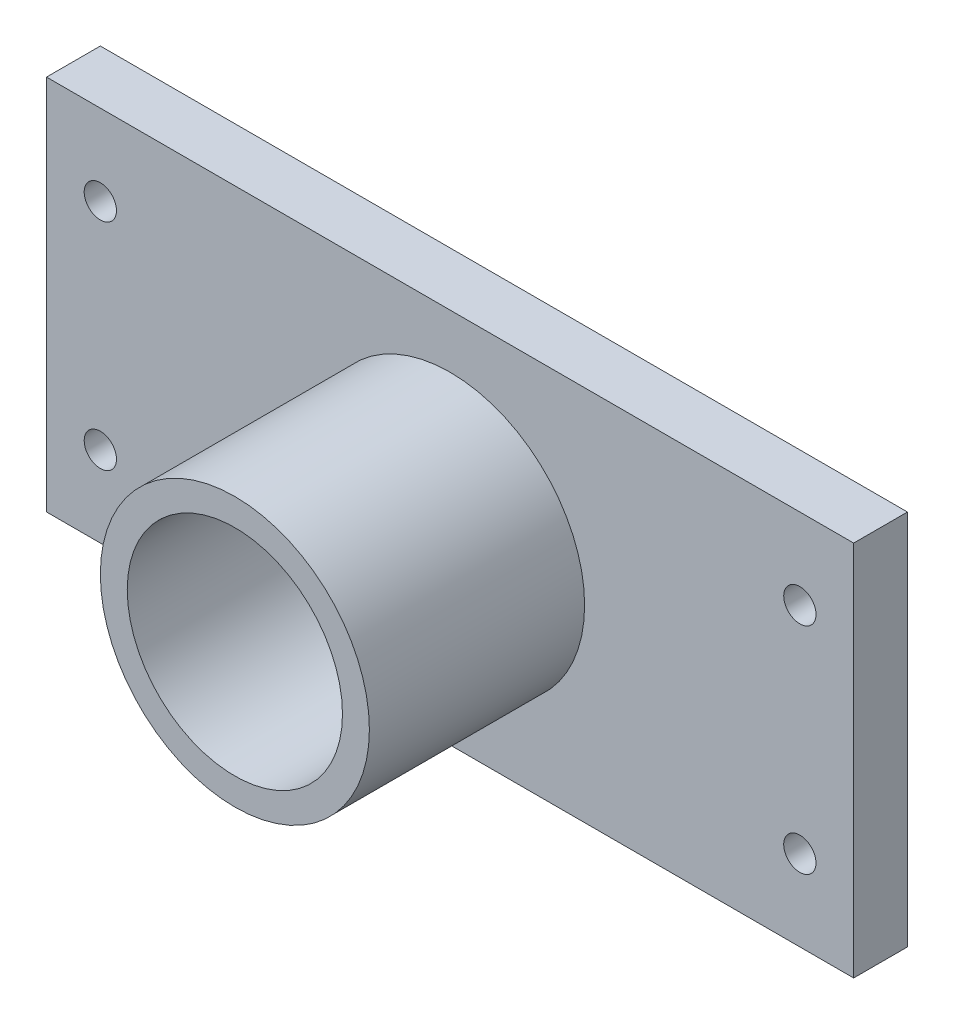
SolidWorks part; units mm, degrees
ref_plane "Front Plane" through (0, 0, 0) normal (0, 0, 1) x (1, 0, 0)
ref_plane "Top Plane" through (0, 0, 0) normal (0, 1, 0) x (1, 0, 0)
ref_plane "Right Plane" through (0, 0, 0) normal (1, 0, 0) x (0, 0, -1)
sketch "Sketch1" plane through (0, 0, 0) normal (0, 0, 1) x (1, 0, 0)
  line L1 (75, 35) -> (-75, 35)
  line L2 (75, 35) -> (75, -35)
  line L3 (75, -35) -> (-75, -35)
  line L4 (-75, 35) -> (-75, -35)
  line L5 (75, 35) -> (-75, -35) construction
  line L6 (75, -35) -> (-75, 35) construction
  circle A0 centre (0, 0) radius 25
  circle A1 centre (0, 0) radius 20
  point P0 (0, 0)
  dimension "D3" = 50
  dimension "D1" = 150
  dimension "D2" = 70
  dimension "D4" = 5
extrude "Boss-Extrude1" add sketch "Sketch1" along normal blind 10 contours L1 L4 L3 L2 A0 | A0 A1 region at (73.3447, 0, 0) region at (-24.2929, 0, 0)
extrude "Boss-Extrude2" add sketch "Sketch1<3>" along normal blind 40 from surface contours A0 A1 region at (-24.2929, 0, 0) starting at face at (0, 0, 10)
sketch "Sketch1<3>" plane through (0, 0, 0) normal (0, 0, 1) x (1, 0, 0) same geometry as "Sketch1"
sketch "Sketch6" plane through (0, 0, 10) normal (0, 0, 1) x (1, 0, 0)
  line L0 (-75, 35) -> (-75, -35) construction
  line L1 (75, 35) -> (-75, 35) construction
  line L2 (-75, 0) -> (0, 0) construction
  line L3 (0, 0) -> (0, 41.0906) construction
  circle A0 centre (-65, 20) radius 3
  circle A1 centre (-65, -20) radius 3
  circle A2 centre (65, -20) radius 3
  circle A3 centre (65, 20) radius 3
  dimension "D1" = 6
  dimension "D2" = 10
  dimension "D3" = 15
extrude "Cut-Extrude1" cut sketch "Sketch6" against normal through all
